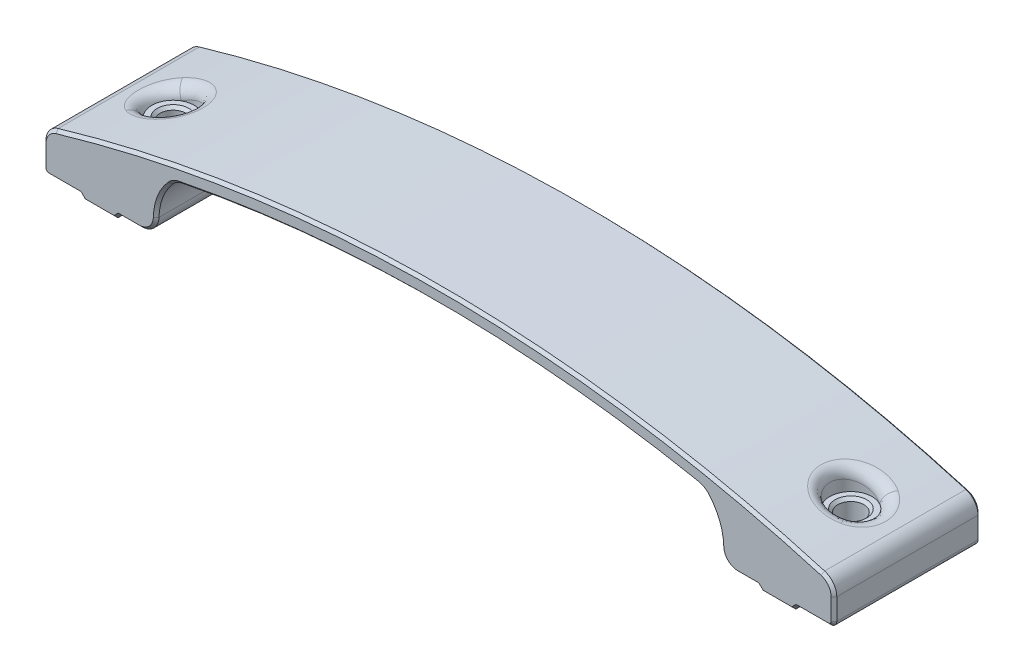
SolidWorks part; units mm, degrees
ref_plane "Front" through (0, 0, 0) normal (0, 0, 1) x (1, 0, 0)
ref_plane "Top" through (0, 0, 0) normal (0, 1, 0) x (1, 0, 0)
ref_plane "Right" through (0, 0, 0) normal (1, 0, 0) x (0, 0, -1)
sketch "Skizze1" plane through (0, 0, 0) normal (0, 0, 1) x (1, 0, 0)
  line L0 (-70, 0) -> (70, 0) construction
  line L1 (70, 0) -> (70, 7)
  line L3 (50, 2.7103) -> (50, 0)
  line L4 (50, 0) -> (70, 0)
  line L5 (0, 0) -> (0, 27.6946) construction
  line L12 (-50, 0) -> (-70, 0)
  line L13 (-50, 2.7103) -> (-50, 0)
  line L15 (-70, 0) -> (-70, 7)
  arc A7 (70, 7) -> (-70, 7) centre (0, -222.6075) ccw
  arc A8 (40.7458, 13.9441) -> (-40.7769, 13.9441) centre (-0.0155, -222.5565) ccw construction
  arc A9 (-41.7479, 12.5564) -> (41.7479, 12.5564) centre (0, -222.6075) cw
  arc A10 (-50, 2.7103) -> (-41.7479, 12.5564) centre (-40, 2.7103) cw
  arc A11 (41.7479, 12.5564) -> (50, 2.7103) centre (40, 2.7103) cw
  point P12 (-50, 10.9411)
  point P20 (50, 10.9411)
  dimension "D4" = 1.2
  dimension "D5" = 10
  dimension "D1" = 20
  dimension "D2" = 7
  dimension "D3" = 140
extrude "Aufsatz-Linear austragen1" add sketch "Skizze1" along normal blind 26
sketch "Skizze2" plane through (0, 0, 26) normal (0, 0, 1) x (1, 0, 0)
  line L0 (50, 0) -> (-50, 0)
  line L6 (50, 0) -> (70, 0)
  line L7 (70, 0) -> (70, 7)
  line L8 (-70, 7) -> (-70, 0)
  line L9 (-70, 0) -> (-50, 0)
  line L10 (-50, 0) -> (-50, 2.7103)
  line L11 (50, 2.7103) -> (50, 0)
  line L12 (50, 0) -> (70, 0)
  line L13 (70, 0) -> (70, 7)
  line L14 (-70, 7) -> (-70, 0)
  line L15 (-70, 0) -> (-50, 0)
  arc A4 (70, 7) -> (-70, 7) centre (0, -222.6075) ccw
  arc A5 (-41.7479, 12.5564) -> (-50, 2.7103) centre (-40, 2.7103) ccw
  arc A6 (41.7479, 12.5564) -> (-41.7479, 12.5564) centre (0, -222.6075) ccw
  arc A7 (50, 2.7103) -> (41.7479, 12.5564) centre (40, 2.7103) ccw
  arc A8 (70, 7) -> (-70, 7) centre (0, -222.6075) ccw
  dimension "D1" = 0
extrude "Aufsatz-Linear austragen2" [suppressed] add sketch "Skizze2" against normal blind 1
sketch "Skizze8" plane through (0, 0, 0) normal (0, 0, -1) x (-1, 0, 0)
  line L0 (-60, 0) -> (-60, -10.9272) construction
  line L1 (-50, 0) -> (-70, 0) construction
  line L2 (-63.5, 0) -> (-56.5, 0)
  line L3 (-56.5, 0) -> (-57.25, -0.75)
  line L4 (-57.25, -0.75) -> (-62.75, -0.75)
  line L5 (-63.5, 0) -> (-62.75, -0.75)
  line L6 (0, 0) -> (0, -16.4832) construction
  line L7 (56.5, 0) -> (57.25, -0.75)
  line L8 (63.5, 0) -> (56.5, 0)
  line L9 (63.5, 0) -> (62.75, -0.75)
  line L10 (57.25, -0.75) -> (62.75, -0.75)
  point P9 (-60, -0.75)
  dimension "D1" = 0.75
  dimension "D2" = 7
  dimension "D3" = 45
extrude "Aufsatz-Linear austragen7" add sketch "Skizze8" against normal up to surface (26 mm away) up to face at (0, 6.1645, 26)
sketch "Skizze3" plane through (0, 0, 0) normal (0, -1, 0) x (1, 0, 0)
  line L0 (-60, 0) -> (-60, 26) construction
  line L2 (-70, 26) -> (-63.5, 26) construction
  line L3 (-57.25, 0) -> (-62.75, 0) construction
  line L5 (0, 0) -> (0, 46.7735) construction
  line L6 (-41.7479, 0) -> (41.7479, 0) construction
  circle A0 centre (-60, 13) radius 2.3
  circle A1 centre (-60, 13) radius 3.75
  circle A2 centre (60, 13) radius 3.75
  circle A3 centre (60, 13) radius 2.3
  dimension "D1" = 4.6
  dimension "D2" = 7.5
extrude "Schnitt-Linear austragen1" cut sketch "Skizze3" against normal through all and the other way blind 10 contours A0 | A3 region at (-60, 0, 13) region at (60, 0, 13)
extrude "Schnitt-Linear austragen2" cut sketch "Skizze3<3>" against normal through all from offset 7 offset against normal yes
sketch "Skizze3<3>" plane through (0, 0, 0) normal (0, -1, 0) x (1, 0, 0) same geometry as "Skizze3"
sketch "Skizze7" plane through (0, 0, 0) normal (0, 0, -1) x (-1, 0, 0)
  line L0 (0, 0) -> (0, 25.3152) construction
  line L1 (-2.5, 14.7333) -> (2.5, 14.7333)
  line L2 (2.5, 14.7333) -> (2.5, 16.2203)
  line L3 (2.5, 16.2203) -> (0, 16.7935)
  line L4 (-2.5, 16.2203) -> (0, 16.7935)
  line L5 (-2.5, 14.7333) -> (-2.5, 16.2203)
  arc A0 (41.7479, 12.5564) -> (-41.7479, 12.5564) centre (0, -222.6075) ccw construction
  point P5 (0, 16.2333)
  point P13 (0, 14.7333)
  dimension "D1" = 5
  dimension "D2" = 1.5
extrude "Aufsatz-Linear austragen6" add sketch "Skizze7" against normal up to surface (26 mm away) up to face at (0, 3.258, 26)
sketch "Skizze6" plane through (0, 0, 0) normal (0, 0, -1) x (-1, 0, 0)
  line L6 (50, 0) -> (56.5, 0)
  line L7 (-50, 0) -> (-50, 2.7103)
  line L8 (50, 2.7103) -> (50, 0)
  line L9 (-56.5, 0) -> (-50, 0)
  line L10 (70, 0) -> (70, 7)
  line L11 (-70, 7) -> (-70, 0)
  line L13 (-56.5, 0) -> (-50, 0)
  line L17 (-2.5, 16.2203) -> (-2.5, 14.7333)
  line L18 (-2.5, 16.2203) -> (-2.5, 14.7333)
  line L19 (-2.5, 14.7333) -> (2.5, 14.7333)
  line L20 (-2.5, 14.7333) -> (2.5, 14.7333)
  line L21 (2.5, 14.7333) -> (2.5, 16.2203)
  line L22 (2.5, 14.7333) -> (2.5, 16.2203)
  line L34 (56.5, 0) -> (57.25, -0.75)
  line L35 (56.5, 0) -> (57.25, -0.75)
  line L36 (57.25, -0.75) -> (62.75, -0.75)
  line L37 (57.25, -0.75) -> (62.75, -0.75)
  line L38 (62.75, -0.75) -> (63.5, 0)
  line L39 (62.75, -0.75) -> (63.5, 0)
  line L40 (63.5, 0) -> (70, 0)
  line L41 (63.5, 0) -> (70, 0)
  line L42 (-70, 0) -> (-63.5, 0)
  line L43 (-70, 0) -> (-63.5, 0)
  line L44 (-63.5, 0) -> (-62.75, -0.75)
  line L45 (-63.5, 0) -> (-62.75, -0.75)
  line L46 (-62.75, -0.75) -> (-57.25, -0.75)
  line L47 (-62.75, -0.75) -> (-57.25, -0.75)
  line L48 (-57.25, -0.75) -> (-56.5, 0)
  line L49 (-57.25, -0.75) -> (-56.5, 0)
  arc A0 (-46.757, 10.0821) -> (46.757, 10.0821) centre (0, -222.6075) cw
  arc A4 (-41.7479, 12.5564) -> (-50, 2.7103) centre (-40, 2.7103) ccw
  arc A5 (-2.5, 16.2203) -> (-41.7479, 12.5564) centre (0, -222.6075) ccw
  arc A6 (50, 2.7103) -> (41.7479, 12.5564) centre (40, 2.7103) ccw
  arc A7 (70, 7) -> (-70, 7) centre (0, -222.6075) ccw
  arc A8 (-41.7479, 12.5564) -> (-46.757, 10.0821) centre (-40, 2.7103) ccw
  arc A9 (-2.5, 16.2203) -> (-41.7479, 12.5564) centre (0, -222.6075) ccw
  arc A10 (46.757, 10.0821) -> (41.7479, 12.5564) centre (40, 2.7103) ccw
  arc A14 (41.7479, 12.5564) -> (2.5, 16.2203) centre (0, -222.6075) ccw
  arc A15 (41.7479, 12.5564) -> (2.5, 16.2203) centre (0, -222.6075) ccw
  arc M14 (-50, 2.7103) -> (-41.7479, 12.5564) centre (-40, 2.7103) cw
  arc M15 (-41.7479, 12.5564) -> (-2.5, 16.2203) centre (0, -222.6075) cw
  arc M16 (41.7479, 12.5564) -> (50, 2.7103) centre (40, 2.7103) cw
  line M38 (2.5, 14.7333) -> (2.5, 16.2203)
  arc M39 (2.5, 16.2203) -> (41.7479, 12.5564) centre (0, -222.6075) cw
  dimension "D2" = 1.5
  dimension "D1" = 0
extrude "Aufsatz-Linear austragen4" add sketch "Skizze6" against normal blind 2 contours A0 M14 M16 M15 | L20 A0 M16 M39 M38 region at (-23.9242, 13.9402, 0) region at (23.9242, 13.9402, 0)
extrude "Aufsatz-Linear austragen5" add sketch "Skizze6<3>" along normal blind 2 from surface contours A0 M14 M16 M15 | L20 A0 M16 M39 M38 region at (-23.9242, 13.9402, 0) region at (23.9242, 13.9402, 0) starting at face at (0, 5.3862, 26)
sketch "Skizze6<3>" plane through (0, 0, 0) normal (0, 0, -1) x (-1, 0, 0) same geometry as "Skizze6"
sketch "Skizze4" [suppressed] plane through (0, 0, 15.5) normal (0, 0, -1) x (-1, 0, 0)
  line L0 (0, 0) -> (0, 24.1531) construction
  line L1 (-2.5, 14.7333) -> (2.5, 14.7333)
  line L2 (2.5, 14.7333) -> (2.5, 16.2203)
  line L3 (2.5, 16.2203) -> (0, 16.737)
  line L4 (-2.5, 16.2203) -> (0, 16.737)
  line L5 (-2.5, 14.7333) -> (-2.5, 16.2203)
  arc A0 (-41.7479, 12.5564) -> (41.7479, 12.5564) centre (0, -222.6075) ccw construction
  point P5 (0, 16.2333)
  point P13 (0, 14.7333)
  dimension "D1" = 5
  dimension "D2" = 1.5
extrude "Aufsatz-Linear austragen3" [suppressed] add sketch "Skizze4" along normal up to surface (15.5 mm away) up to face at (0, 2.9084, 0)
sketch "Skizze9" plane through (0, 0, 0) normal (0, -1, 0) x (1, 0, 0)
  circle A0 centre (-60, 13) radius 4.15
  circle A1 centre (60, 13) radius 4.15
  dimension "D1" = 8.3
extrude "Schnitt-Linear austragen3" cut sketch "Skizze9" along normal blind 10
fillet "Verrundung1" radius 3 8 edges at (-50, 0, 13) (-70, 7, 13) (70, 7, 13) (46.757, 10.0821, 1) (-46.757, 10.0821, 1) (-46.757, 10.0821, 25) (50, 0, 13) (46.757, 10.0821, 25)
fillet "Verrundung2" radius 1 2 edges at (-70, 0, 13) (70, 0, 13)
chamfer "Fase1" [suppressed] distance 3 angle 45
chamfer "Fase3" distance 1.5 angle 45 8 edges at (44.9155, 11.4188, 24) (22.1997, 15.1994, 24) (-44.9155, 11.4188, 24) (-22.1997, 15.1994, 24) (-44.9155, 11.4188, 2) (-22.1997, 15.1994, 2) (44.9155, 11.4188, 2) (22.1997, 15.1994, 2)
chamfer "Fase2" distance 0.5 angle 45 52 edges at (-50.8992, 0.8552, 0) (-49.3214, 6.3313, 0) (49.3214, 6.3313, 0) (70, 2.8837, 0) (69.4025, 6.5641, 0) (0, 17.4333, 0) (-69.4025, 6.5641, 0) (-70, 2.8837, 0) (-69.7071, 0.2929, 0) (-66.25, 0, 0) (-54.7484, 0, 0) (-69.4025, 6.5641, 26) (0, 17.4333, 26) (69.4025, 6.5641, 26) (70, 2.8837, 26) (-66.25, 0, 26) (-69.7071, 0.2929, 26) (-70, 2.8837, 26) (-60, 7, 10.7) (60, 7, 15.3) (60, 0, 10.7) (-46.7674, 9.9181, 0) (46.7674, 9.9181, 0) (-60, 0, 10.7) (49.3214, 6.3313, 26) (-49.3214, 6.3313, 26) (-50.8992, 0.8552, 26) (0, 14.7333, 0) (0, 14.7333, 26) (50.8992, 0.8552, 0) (50.8992, 0.8552, 26) (46.7674, 9.9181, 26) (-46.7674, 9.9181, 26) (69.7071, 0.2929, 0) (69.7071, 0.2929, 26) (-63.125, -0.375, 0) (-60, -0.75, 0) (-56.875, -0.375, 0) (54.7484, 0, 0) (56.875, -0.375, 0) (60, -0.75, 0) (63.125, -0.375, 0) (66.25, 0, 0) (63.125, -0.375, 26) (60, -0.75, 26) (56.875, -0.375, 26) (54.7484, 0, 26) (-54.7484, 0, 26) (-56.875, -0.375, 26) (-60, -0.75, 26) (-63.125, -0.375, 26) (66.25, 0, 26)
fillet "Verrundung3" radius 2 2 edges at (59.116, 10.0401, 16.6443) (-60.8742, 9.5863, 16.6467)
fillet "Verrundung4" radius 0.73 4 edges at (-2.5, 14.7333, 13) (-2.5, 16.2203, 13) (2.5, 16.2203, 13) (2.5, 14.7333, 13)
fillet "Verrundung5" radius 0.75 4 edges at (60, -0.75, 17.15) (60, -0.75, 8.85) (-60, -0.75, 17.15) (-60, -0.75, 8.85)
